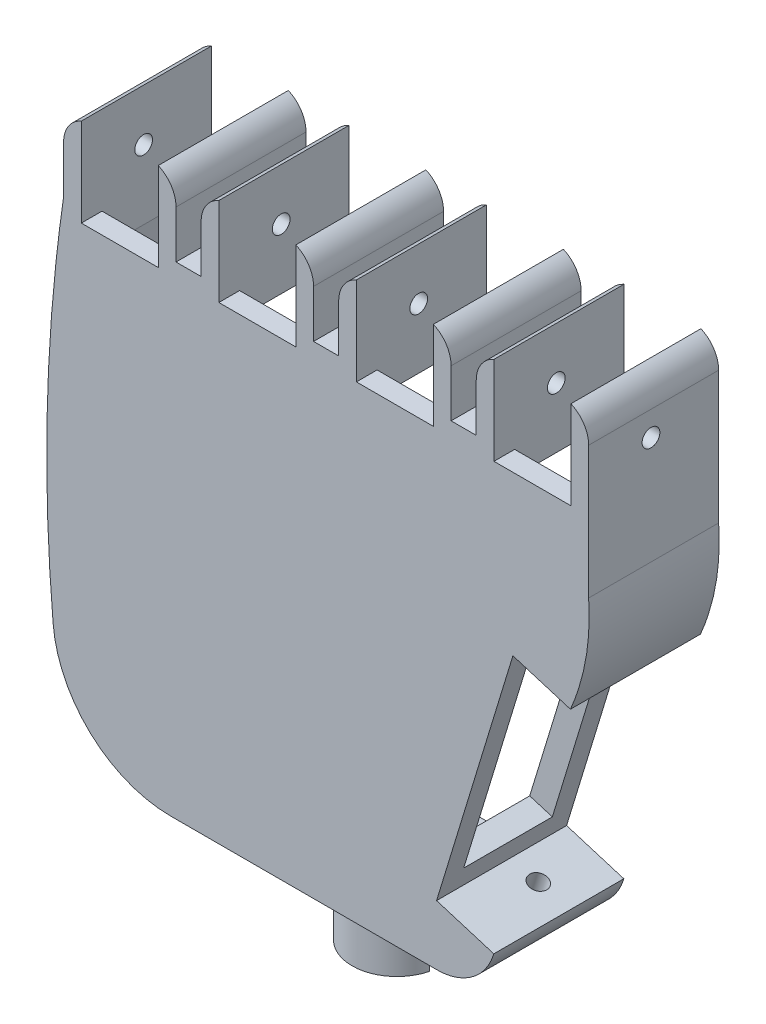
SolidWorks part; units mm, degrees
ref_plane "Front Plane" through (0, 0, 0) normal (0, 0, 1) x (1, 0, 0)
ref_plane "Top Plane" through (0, 0, 0) normal (0, 1, 0) x (1, 0, 0)
ref_plane "Right Plane" through (0, 0, 0) normal (1, 0, 0) x (0, 0, -1)
sketch "Sketch3" plane through (0, 0, 0) normal (0, 0, 1) x (1, 0, 0)
  line L3 (-47.4183, -62.0432) -> (-2.3603, -62.0432)
  line L5 (7.2884, -54.6705) -> (-2.3929, -51.7173)
  line L6 (20, -13) -> (10.3187, -10.0467)
  line L7 (10.3187, -10.0467) -> (-2.3929, -51.7173)
  line L8 (23.2745, 5.2791) -> (23.2745, 32.2474)
  line L9 (23.2745, 32.2474) -> (20.2745, 32.2474)
  line L10 (20.2745, 32.2474) -> (20.2745, 17.2959)
  line L11 (-65.5734, 32.2474) -> (-62.5734, 32.2474)
  line L12 (-62.5734, 32.2474) -> (-62.5734, 17.2959)
  line L13 (-49.549, 17.2959) -> (-49.549, 32.2474)
  line L14 (-49.549, 32.2474) -> (-46.549, 32.2474)
  line L15 (-46.549, 32.2474) -> (-46.549, 19.6031)
  line L16 (-42.2989, 19.6031) -> (-42.2989, 32.2474)
  line L17 (-42.2989, 32.2474) -> (-39.2989, 32.2474)
  line L18 (-39.2989, 32.2474) -> (-39.2989, 17.2959)
  line L19 (-62.5734, 17.2959) -> (-49.549, 17.2959)
  line L20 (-46.549, 19.6031) -> (-42.2989, 19.6031)
  line L21 (-39.2989, 17.2959) -> (-26.2745, 17.2959)
  line L22 (-26.2745, 17.2959) -> (-26.2745, 32.2474)
  line L23 (-26.2745, 32.2474) -> (-23.2745, 32.2474)
  line L24 (-23.2745, 32.2474) -> (-23.2745, 19.6031)
  line L25 (-23.2745, 19.6031) -> (-19.0244, 19.6031)
  line L26 (-19.0244, 19.6031) -> (-19.0244, 32.2474)
  line L27 (-19.0244, 32.2474) -> (-16.0244, 32.2474)
  line L28 (-16.0244, 32.2474) -> (-16.0244, 17.2959)
  line L29 (-16.0244, 17.2959) -> (-3, 17.2959)
  line L30 (-3, 17.2959) -> (-3, 32.2474)
  line L31 (-3, 32.2474) -> (0, 32.2474)
  line L32 (0, 32.2474) -> (0, 19.6031)
  line L33 (0, 19.6031) -> (4.2501, 19.6031)
  line L34 (4.2501, 19.6031) -> (4.2501, 32.2474)
  line L35 (4.2501, 32.2474) -> (7.2501, 32.2474)
  line L36 (7.2501, 32.2474) -> (7.2501, 17.2959)
  line L37 (7.2501, 17.2959) -> (20.2745, 17.2959)
  line L38 (-65.5734, 19.6334) -> (-65.5734, 32.2474)
  arc A0 (-67.3511, -43.681) -> (-47.4183, -62.0432) centre (-47.4183, -42.0432) ccw
  arc A1 (7.2884, -54.6705) -> (-2.3603, -62.0432) centre (-2.3603, -52.0432) cw
  spline S0 degree 2 poles (-67.3511, -43.681) (-70.165, -11.9081) (-65.5734, 19.6334) knots 0 0 0 1 1 1
  spline S1 degree 2 poles (23.2745, 5.2791) (23.9192, -4.1434) (20, -13) knots 0 0 0 1 1 1
  dimension "D3" = 20
  dimension "D2" = 10
  dimension "D1" = 13.0244
  dimension "D4" = 3
  dimension "D5" = 4.2501
extrude "Boss-Extrude3" add sketch "Sketch3" along normal blind 22 contours L29 L30 L31 L32 L33 L34 L35 L36 L37 L10 L9 L8 S1 L6 L7 L5 A1 L3 A0 S0 L38 L11 L12 L19 L13 L14 L15 L20 L16 L17 L18 L21 L22 L23 L24 L25 L26 L27 L28
shell "Shell4" thickness 4 removed face at (-19.4945, 12.0927, 0)
fillet "Fillet1" radius 5 1 edges at (-65.5734, 32.2474, 11)
fillet "Fillet2" radius 5 7 edges at (23.2745, 32.2474, 11) (4.2501, 32.2474, 11) (0, 32.2474, 11) (-19.0244, 32.2474, 11) (-23.2745, 32.2474, 11) (-42.2989, 32.2474, 11) (-46.549, 32.2474, 11)
sketch "Sketch27" plane through (-0.7583, -2.4857, 0) normal (0.2918, 0.9565, 0) x (0.9565, -0.2918, 0)
  circle A0 centre (17.5061, -9.2871) radius 1.5
  circle A1 centre (17.5061, -9.2871) radius 1.5
hole_wizard "Ø3.0 (3) Diameter Hole6" positions "Sketch30" profile "Sketch31" hole size "Ø3.0" standard "ANSI Metric" end condition through all
sketch "Sketch30" plane through (-0.7583, -2.4857, 0) normal (0.2918, 0.9565, 0) x (0.9565, -0.2918, 0)
  point P0 (17.5061, -9.2871)
sketch "Sketch31" plane through (15.9861, -7.5936, 9.2871) normal (0, 0, 1) x (-0.9565, 0.2918, 0)
  line L0 (0, 0) -> (0, 76.8066)
  line L1 (0, 76.8066) -> (1.5, 76.8066)
  line L2 (1.5, 76.8066) -> (1.5, 0)
  line L5 (1.5, 0) -> (0, 0)
  line L11 (0, -6.35) -> (0, 107.95) construction
  dimension "Thru Hole Dia." = 3
  dimension "Thru Hole Depth" = 76.8066
sketch "Sketch32" plane through (-65.5734, 0, 0) normal (-1, 0, 0) x (0, 0, 1)
  circle A0 centre (11.4541, 23.5066) radius 1.5
hole_wizard "Ø3.0 (3) Diameter Hole7" positions "Sketch33" profile "Sketch34" hole size "Ø3.0" standard "ANSI Metric" end condition through all
sketch "Sketch33" plane through (-65.5734, 0, 0) normal (-1, 0, 0) x (0, 0, 1)
  point P0 (11.4541, 23.5066)
sketch "Sketch34" plane through (-65.5734, 23.5066, 11.4541) normal (0, 1, 0) x (0, 0, 1)
  line L0 (0, 0) -> (0, 89.1703)
  line L1 (0, 89.1703) -> (1.5, 89.1703)
  line L2 (1.5, 89.1703) -> (1.5, 0)
  line L5 (1.5, 0) -> (0, 0)
  line L11 (0, -6.35) -> (0, 107.95) construction
  dimension "Thru Hole Dia." = 3
  dimension "Thru Hole Depth" = 89.1703
sketch "Sketch35" plane through (12.2441, -3.7351, 0) normal (0.9565, -0.2918, 0) x (0, 0, -1)
  line L1 (0, -6.5988) -> (-22, -6.5988)
  line L2 (0, -6.5988) -> (0, -50.1651)
  line L3 (0, -50.1651) -> (-22, -50.1651)
  line L4 (-22, -6.5988) -> (-22, -50.1651)
  dimension "D1" = 43.5663
  dimension "D2" = 22
sketch "Sketch36" plane through (-1.9254, -6.3117, 0) normal (-0.2918, -0.9565, 0) x (0.9565, -0.2918, 0)
  line L1 (22.9228, 0) -> (12.8011, 0)
  line L2 (22.9228, 0) -> (22.9228, 22)
  line L3 (22.9228, 22) -> (12.8011, 22)
  line L4 (12.8011, 0) -> (12.8011, 22)
  dimension "D1" = 10.1217
sketch "Sketch37" plane through (12.2441, -3.7351, 0) normal (0.9565, -0.2918, 0) x (0, 0, -1)
  line L0 (0, -6.5988) -> (0, -50.1651) construction
  line L1 (-18.5, -10.0988) -> (-3.5, -10.0988)
  line L2 (-18.5, -10.0988) -> (-18.5, -46.6651)
  line L3 (-18.5, -46.6651) -> (-3.5, -46.6651)
  line L4 (-3.5, -10.0988) -> (-3.5, -46.6651)
  line L5 (-22, -6.5988) -> (-22, -50.1651) construction
  line L6 (0, -6.5988) -> (-22, -6.5988) construction
  line L7 (0, -50.1651) -> (-22, -50.1651) construction
  dimension "D1" = 3.5
  dimension "D2" = 3.5
  dimension "D3" = 3.5
  dimension "D4" = 3.5
extrude "Cut-Extrude1" cut sketch "Sketch37" against normal blind 10 contours L1 L4 L3 L2
sketch "Sketch41" plane through (0, 17.2959, 0) normal (0, 1, 0) x (1, 0, 0)
  line L0 (20.2745, -22) -> (20.2745, 0) construction
  line L1 (20.2745, -3.5) -> (7.2501, -3.5)
  line L2 (20.2745, -3.5) -> (20.2745, -18.5)
  line L3 (20.2745, -18.5) -> (7.2501, -18.5)
  line L4 (7.2501, -3.5) -> (7.2501, -18.5)
  line L5 (7.2501, -22) -> (7.2501, 0) construction
  line L6 (-3, -22) -> (-3, 0) construction
  line L7 (-3, -3.5) -> (-16.0244, -3.5)
  line L8 (-3, -3.5) -> (-3, -18.5)
  line L9 (-3, -18.5) -> (-16.0244, -18.5)
  line L10 (-16.0244, -3.5) -> (-16.0244, -18.5)
  line L11 (-16.0244, -22) -> (-16.0244, 0) construction
  line L12 (-26.2745, -22) -> (-26.2745, 0) construction
  line L13 (-26.2745, -3.5) -> (-39.2989, -3.5)
  line L14 (-26.2745, -3.5) -> (-26.2745, -18.5)
  line L15 (-26.2745, -18.5) -> (-39.2989, -18.5)
  line L16 (-39.2989, -3.5) -> (-39.2989, -18.5)
  line L17 (-39.2989, -22) -> (-39.2989, 0) construction
  line L18 (-49.549, -22) -> (-49.549, 0) construction
  line L19 (-49.549, -3.5) -> (-62.5734, -3.5)
  line L20 (-49.549, -3.5) -> (-49.549, -18.5)
  line L21 (-49.549, -18.5) -> (-62.5734, -18.5)
  line L22 (-62.5734, -3.5) -> (-62.5734, -18.5)
  line L23 (-62.5734, -22) -> (-62.5734, 0) construction
  line L24 (7.2501, -22) -> (20.2745, -22) construction
  line L25 (20, 0) -> (10.3187, 0) construction
  dimension "D1" = 3.5
  dimension "D2" = 3.5
extrude "Cut-Extrude2" cut sketch "Sketch41" against normal blind 10 contours L3 L4 L1 L2
extrude "Cut-Extrude3" cut sketch "Sketch41<3>" against normal blind 10
sketch "Sketch41<3>" plane through (0, 17.2959, 0) normal (0, 1, 0) x (1, 0, 0) same geometry as "Sketch41"
sketch "Sketch42" plane through (-1.9254, -6.3117, 0) normal (-0.2918, -0.9565, 0) x (0.9565, -0.2918, 0)
  line L0 (16.0061, 9.2871) -> (12.8156, 9.2871)
  circle A0 centre (17.5061, 9.2871) radius 1.5 construction
sketch "Sketch43" plane through (20.2745, 0, 0) normal (-1, 0, 0) x (0, 0, 1)
  line L0 (11, 32.2474) -> (11.4541, 23.5066) construction
  line L1 (22, 32.2474) -> (0, 32.2474) construction
  line L3 (0, 32.2474) -> (22, 32.2474)
  dimension "D1" = 22
sketch "Sketch44" plane through (0, -62.0432, 0) normal (0, -1, 0) x (1, 0, 0)
  line L0 (-20.1591, 22) -> (-20.1591, 11) construction
  line L1 (-47.4183, 22) -> (-2.3603, 22) construction
  circle A0 centre (-20.1591, 11) radius 11 construction
  circle A1 centre (-20.1591, 11) radius 7.6
extrude "Boss-Extrude4" add sketch "Sketch44" along normal blind 10 contours A1
sketch "Sketch60" plane through (0, -72.0432, 0) normal (0, -1, 0) x (1, 0, 0)
  line L0 (-17.8296, 12.7553) -> (-18.3716, 12.6261)
  line L1 (-18.3716, 12.6261) -> (-18.1935, 13.1544)
  line L2 (-18.1935, 13.1544) -> (-18.7025, 12.9278)
  line L3 (-18.7025, 12.9278) -> (-18.6246, 13.4798)
  line L4 (-18.6246, 13.4798) -> (-19.0833, 13.1636)
  line L5 (-19.0833, 13.1636) -> (-19.1082, 13.7205)
  line L6 (-19.1082, 13.7205) -> (-19.5009, 13.3253)
  line L7 (-19.5009, 13.3253) -> (-19.6277, 13.8682)
  line L8 (-19.6277, 13.8682) -> (-19.9412, 13.4076)
  line L9 (-19.9412, 13.4076) -> (-20.1655, 13.9179)
  line L10 (-20.1655, 13.9179) -> (-20.389, 13.4075)
  line L11 (-20.389, 13.4075) -> (-20.7033, 13.868)
  line L12 (-20.7033, 13.868) -> (-20.8292, 13.3252)
  line L13 (-20.8292, 13.3252) -> (-21.2228, 13.72)
  line L14 (-21.2228, 13.72) -> (-21.2468, 13.1634)
  line L15 (-21.2468, 13.1634) -> (-21.7062, 13.4792)
  line L16 (-21.7062, 13.4792) -> (-21.6276, 12.9276)
  line L17 (-21.6276, 12.9276) -> (-22.1372, 13.1536)
  line L18 (-22.1372, 13.1536) -> (-21.9585, 12.6259)
  line L19 (-21.9585, 12.6259) -> (-22.501, 12.7544)
  line L20 (-22.501, 12.7544) -> (-22.2284, 12.2685)
  line L21 (-22.2284, 12.2685) -> (-22.7852, 12.2951)
  line L22 (-22.7852, 12.2951) -> (-22.428, 11.8676)
  line L23 (-22.428, 11.8676) -> (-22.981, 11.7887)
  line L24 (-22.981, 11.7887) -> (-22.5505, 11.4368)
  line L25 (-22.5505, 11.4368) -> (-23.0793, 11.2613)
  line L26 (-23.0793, 11.2613) -> (-22.5918, 10.9909)
  line L27 (-22.5918, 10.9909) -> (-23.0793, 10.7212)
  line L28 (-23.0793, 10.7212) -> (-22.5504, 10.5449)
  line L29 (-22.5504, 10.5449) -> (-22.9801, 10.1902)
  line L30 (-22.9801, 10.1902) -> (-22.4278, 10.1142)
  line L31 (-22.4278, 10.1142) -> (-22.785, 9.6866)
  line L32 (-22.785, 9.6866) -> (-22.2282, 9.7133)
  line L33 (-22.2282, 9.7133) -> (-22.5007, 9.2274)
  line L34 (-22.5007, 9.2274) -> (-21.9583, 9.356)
  line L35 (-21.9583, 9.356) -> (-22.1368, 8.8282)
  line L36 (-22.1368, 8.8282) -> (-21.6273, 9.0543)
  line L37 (-21.6273, 9.0543) -> (-21.7058, 8.5027)
  line L38 (-21.7058, 8.5027) -> (-21.2465, 8.8185)
  line L39 (-21.2465, 8.8185) -> (-21.2224, 8.2619)
  line L40 (-21.2224, 8.2619) -> (-20.8289, 8.6568)
  line L41 (-20.8289, 8.6568) -> (-20.7029, 8.1141)
  line L42 (-20.7029, 8.1141) -> (-20.3887, 8.5745)
  line L43 (-20.3887, 8.5745) -> (-20.1651, 8.0642)
  line L44 (-20.1651, 8.0642) -> (-19.9408, 8.5746)
  line L45 (-19.9408, 8.5746) -> (-19.6273, 8.114)
  line L46 (-19.6273, 8.114) -> (-19.5006, 8.6569)
  line L47 (-19.5006, 8.6569) -> (-19.1078, 8.2618)
  line L48 (-19.1078, 8.2618) -> (-19.083, 8.8187)
  line L49 (-19.083, 8.8187) -> (-18.6243, 8.5025)
  line L50 (-18.6243, 8.5025) -> (-18.7023, 9.0545)
  line L51 (-18.7023, 9.0545) -> (-18.1932, 8.828)
  line L52 (-18.1932, 8.828) -> (-18.3713, 9.3562)
  line L53 (-18.3713, 9.3562) -> (-17.8293, 9.2271)
  line L54 (-17.8293, 9.2271) -> (-18.1015, 9.7136)
  line L55 (-18.1015, 9.7136) -> (-17.545, 9.6863)
  line L56 (-17.545, 9.6863) -> (-17.9019, 10.1145)
  line L57 (-17.9019, 10.1145) -> (-17.3496, 10.1906)
  line L58 (-17.3496, 10.1906) -> (-17.7793, 10.5453)
  line L59 (-17.7793, 10.5453) -> (-17.2505, 10.7216)
  line L60 (-17.2505, 10.7216) -> (-17.738, 10.9912)
  line L61 (-17.738, 10.9912) -> (-17.2506, 11.2617)
  line L62 (-17.2506, 11.2617) -> (-17.7794, 11.4372)
  line L63 (-17.7794, 11.4372) -> (-17.3499, 11.7926)
  line L64 (-20.1591, 18.6) -> (-20.1591, 11) construction
  line L65 (-17.3499, 11.7926) -> (-17.902, 11.8679)
  line L66 (-17.902, 11.8679) -> (-17.5452, 12.2962)
  line L67 (-17.5452, 12.2962) -> (-18.1016, 12.2688)
  line L68 (-18.1016, 12.2688) -> (-17.8296, 12.7553)
  line L69 (-20.1651, 10.9912) -> (-20.1651, 8.0642) construction
  circle A0 centre (-20.1591, 11) radius 7.6 construction
extrude "Cut-Extrude12" cut sketch "Sketch60" against normal blind 2
sketch "Sketch65" plane through (0, -62.0432, 0) normal (0, -1, 0) x (1, 0, 0)
  line L0 (-20.1591, 11) -> (-28.3826, 11) construction
  circle A0 centre (-28.3826, 11) radius 2
  circle A1 centre (-12.1658, 11) radius 2
extrude "Cut-Extrude15" cut sketch "Sketch65" against normal blind 8 and the other way blind 12
ref_plane "Plane1" through (26.5914, -8.1117, 0) normal (0.9565, -0.2918, 0) x (0, 0, -1)
sketch "Sketch66" plane through (26.5914, -8.1117, 0) normal (0.9565, -0.2918, 0) x (0, 0, -1)
  line L1 (0.779, -6.1257) -> (-23.3012, -6.1257)
  line L2 (0.779, -6.1257) -> (0.779, -7.4642)
  line L3 (0.779, -7.4642) -> (-23.3012, -7.4642)
  line L4 (-23.3012, -6.1257) -> (-23.3012, -7.4642)
  line L5 (0.779, -6.1257) -> (-23.3012, -7.4642) construction
  line L6 (0.779, -7.4642) -> (-23.3012, -6.1257) construction
  line L7 (0.8167, -49.0185) -> (-23.3012, -49.0185)
  line L8 (0.8167, -49.0185) -> (0.8167, -50.3898)
  line L9 (0.8167, -50.3898) -> (-23.3012, -50.3898)
  line L10 (-23.3012, -49.0185) -> (-23.3012, -50.3898)
  line L11 (0.8167, -49.0185) -> (-23.3012, -50.3898) construction
  line L12 (0.8167, -50.3898) -> (-23.3012, -49.0185) construction
  point P4 (-11.2611, -6.7949)
  point P9 (-11.2422, -49.7042)
  point P10 (0.8781, -5.6528)
  point P11 (0.779, -6.1257)
  point P12 (0.8167, -50.3898)
extrude "Cut-Extrude16" cut sketch "Sketch66" against normal up to surface (15 mm away) up to face at (3.9629, -30.882, 11)
